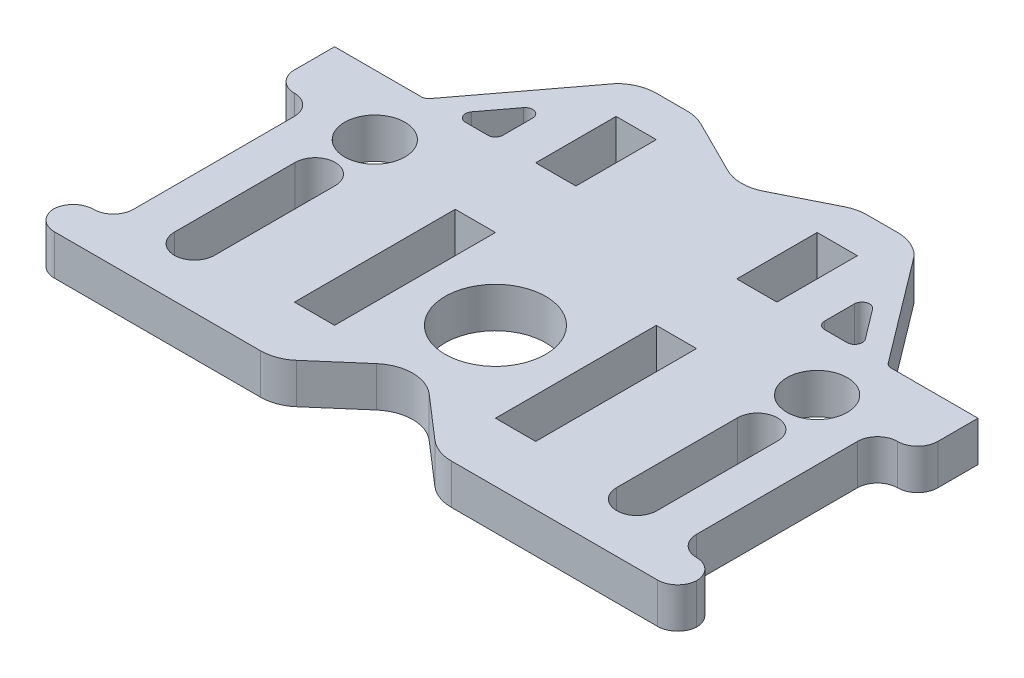
SolidWorks part; units mm, degrees
ref_plane "Front Plane" through (0, 0, 0) normal (0, 0, 1) x (1, 0, 0)
ref_plane "Top Plane" through (0, 0, 0) normal (0, 1, 0) x (1, 0, 0)
ref_plane "Right Plane" through (0, 0, 0) normal (1, 0, 0) x (0, 0, -1)
sketch "Sketch1" plane through (0, 0, 0) normal (0, 1, 0) x (1, 0, 0)
  line L0 (0, 12.7) -> (0, -12.7) construction
  line L1 (25.4, -12.7) -> (23.8125, -12.7)
  line L2 (25.4, -12.7) -> (25.4, -9.525)
  line L3 (25.4, 12.7) -> (23.8125, 12.7)
  line L4 (-25.4, -12.7) -> (-25.4, -9.525)
  line L5 (-25.4, -31.75) -> (-25.4, -12.7)
  line L6 (-6.35, 6.35) -> (-9.525, 6.35)
  line L7 (-6.35, 6.35) -> (-6.35, -6.35)
  line L8 (-6.35, -6.35) -> (-9.525, -6.35)
  line L9 (-9.525, 6.35) -> (-9.525, -6.35)
  line L10 (-3.175, -12.7) -> (-13.2935, -34.4304)
  line L11 (-19.05, -12.7) -> (-19.05, -22.225)
  line L12 (-15.0293, -23.1152) -> (-10.1796, -12.7)
  line L13 (-10.1796, -12.7) -> (-19.05, -12.7)
  line L14 (25.4, 0) -> (-25.4, 0) construction
  line L15 (-22.225, 6.35) -> (-22.225, -6.35)
  line L16 (-23.8125, 12.7) -> (-23.8125, -18.6877) construction
  line L17 (-25.4, 9.525) -> (-25.4, 12.7)
  line L18 (23.8125, 12.7) -> (23.8125, -18.6877) construction
  line L19 (25.4, 9.525) -> (25.4, 12.7)
  line L20 (22.225, 6.35) -> (22.225, -6.35)
  line L21 (10.1796, -12.7) -> (19.05, -12.7)
  line L22 (15.0293, -23.1152) -> (10.1796, -12.7)
  line L23 (19.05, -12.7) -> (19.05, -22.225)
  line L24 (3.175, -12.7) -> (13.2935, -34.4304)
  line L25 (9.525, 6.35) -> (9.525, -6.35)
  line L26 (6.35, -6.35) -> (9.525, -6.35)
  line L27 (6.35, 6.35) -> (6.35, -6.35)
  line L28 (6.35, 6.35) -> (9.525, 6.35)
  line L29 (25.4, -31.75) -> (25.4, -12.7)
  line L30 (25.4, -12.7) -> (25.4, -9.525)
  line L31 (25.4, 9.525) -> (25.4, 12.7)
  line L32 (3.175, -12.7) -> (-3.175, -12.7)
  line L33 (-6.35, 22.225) -> (-9.525, 22.225)
  line L34 (-6.35, 12.7) -> (-9.525, 12.7)
  line L35 (-6.35, 12.7) -> (-6.35, 19.05)
  line L36 (-6.35, 19.05) -> (-9.525, 19.05)
  line L37 (-9.525, 12.7) -> (-9.525, 19.05)
  line L38 (-23.8125, 12.7) -> (-18.2563, 12.7)
  line L39 (-6.35, 22.225) -> (0, 19.05)
  line L40 (16.2674, 12.7) -> (12.7, 12.7)
  line L41 (12.7, 17.4273) -> (16.2674, 12.7)
  line L42 (11.7701, 21.2951) -> (18.2563, 12.7)
  line L43 (6.35, 12.7) -> (9.525, 12.7)
  line L44 (-12.7, 12.7) -> (-12.7, 17.4273)
  line L45 (12.7, 12.7) -> (12.7, 17.4273)
  line L46 (-23.8125, 12.7) -> (-25.4, 12.7)
  line L47 (-6.35, 12.7) -> (-9.525, 12.7)
  line L48 (23.8125, 12.7) -> (18.2563, 12.7)
  line L49 (-11.7701, 21.2951) -> (-18.2563, 12.7)
  line L50 (-12.7, 17.4273) -> (-16.2674, 12.7)
  line L51 (-16.2674, 12.7) -> (-12.7, 12.7)
  line L52 (-10.5029, 20.3388) -> (-16.9891, 11.7437) construction
  line L53 (9.525, 12.7) -> (9.525, 19.05)
  line L54 (6.35, 12.7) -> (6.35, 19.05)
  line L55 (6.35, 12.7) -> (9.525, 12.7)
  line L56 (6.35, 22.225) -> (0, 19.05)
  line L57 (6.35, 19.05) -> (9.525, 19.05)
  line L58 (6.35, 22.225) -> (9.525, 22.225)
  circle A0 centre (-19.05, -31.75) radius 3.175
  arc A1 (-25.4, -31.75) -> (-13.2935, -34.4304) centre (-19.05, -31.75) ccw
  arc A2 (-15.0293, -23.1152) -> (-19.05, -22.225) centre (-19.05, -31.75) ccw
  circle A3 centre (-19.05, -31.75) radius 6.35 construction
  arc A4 (-23.8125, -7.9375) -> (-25.4, -9.525) centre (-23.8125, -9.525) ccw
  circle A5 centre (-19.05, -31.75) radius 9.525 construction
  arc A6 (-23.8125, -7.9375) -> (-22.225, -6.35) centre (-23.8125, -6.35) ccw
  arc A7 (-23.8125, 7.9375) -> (-22.225, 6.35) centre (-23.8125, 6.35) cw
  arc A8 (-23.8125, 7.9375) -> (-25.4, 9.525) centre (-23.8125, 9.525) cw
  arc A9 (23.8125, 7.9375) -> (25.4, 9.525) centre (23.8125, 9.525) ccw
  arc A10 (23.8125, 7.9375) -> (22.225, 6.35) centre (23.8125, 6.35) ccw
  arc A11 (23.8125, -7.9375) -> (22.225, -6.35) centre (23.8125, -6.35) cw
  arc A12 (23.8125, -7.9375) -> (25.4, -9.525) centre (23.8125, -9.525) cw
  arc A13 (15.0293, -23.1152) -> (19.05, -22.225) centre (19.05, -31.75) cw
  arc A14 (25.4, -31.75) -> (13.2935, -34.4304) centre (19.05, -31.75) cw
  circle A15 centre (19.05, -31.75) radius 3.175
  arc A16 (-11.7701, 21.2951) -> (-9.525, 22.225) centre (-9.525, 19.05) cw
  arc A17 (11.7701, 21.2951) -> (9.525, 22.225) centre (9.525, 19.05) ccw
  point P17 (-12.7, -31.75)
  point P21 (-9.525, -31.75)
  dimension "D7" = 6.35
  dimension "D1" = 50.8
  dimension "D2" = 25.4
  dimension "D3" = 3.175
  dimension "D4" = 12.7
  dimension "D5" = 6.35
  dimension "D6" = 6.35
  dimension "D8" = 44.45
  dimension "D9" = 19.05
  dimension "D11" = 3.175
  dimension "D13" = 6.35
  dimension "D14" = 6.35
  dimension "D15" = 3.175
  dimension "D16" = 1.5875
  dimension "D17" = 9.525
  dimension "D18" = 6.35
  dimension "D19" = 3.175
  dimension "D10" = 3.175
  dimension "D12" = 6.35
  dimension "D22" = 1.5875
extrude "Boss-Extrude1" add sketch "Sketch1" along normal blind 3.175 contours A14 L29 L2 A12 A11 L20 A10 A9 L19 L3 L17 A8 A7 L15 A6 A4 L4 L5 A1 L10 L32 L24 L12 A2 L11 L13 L27 L28 L25 L26 L9 L6 L7 L8 A0 A13 L22 L21 L23 A15 region at (0, 0, 5.8577)
fillet "Fillet1" radius 1.5875 6 edges at (19.05, 1.5875, 12.7) (10.1796, 1.5875, 12.7) (3.175, 1.5875, 12.7) (-3.175, 1.5875, 12.7) (-10.1796, 1.5875, 12.7) (-19.05, 1.5875, 12.7)
sketch "Sketch2" plane through (0, 3.175, 0) normal (0, 1, 0) x (1, 0, 0)
  line L0 (25.4, 12.7) -> (18.2563, 12.7) construction
  line L1 (-22.225, 6.35) -> (-22.225, -6.35) construction
  circle A0 centre (-17.4625, 7.9375) radius 2.3813
  circle A1 centre (17.4625, 7.9375) radius 2.3813
  dimension "D1" = 4.7625
  dimension "D2" = 4.7625
  dimension "D3" = 4.7625
extrude "Cut-Extrude1" cut sketch "Sketch2" against normal through all
fillet "Fillet2" radius 3.175 3 edges at (6.35, 1.5875, -22.225) (0, 1.5875, -19.05) (-6.35, 1.5875, -22.225)
fillet "Fillet4" radius 0.6 8 edges at (12.7, 1.5875, -12.7) (12.7, 1.5875, -17.4273) (-12.7, 1.5875, -17.4273) (-16.2674, 1.5875, -12.7) (-12.7, 1.5875, -12.7) (18.2563, 1.5875, -12.7) (16.2674, 1.5875, -12.7) (-18.2563, 1.5875, -12.7)
sketch "Sketch3" plane through (0, 3.175, 0) normal (0, 1, 0) x (1, 0, 0)
  line L1 (-31.6131, -11.0137) -> (27.6819, -11.0137)
  line L2 (-31.6131, -11.0137) -> (-31.6131, -41.4937)
  line L3 (-31.6131, -41.4937) -> (27.6819, -41.4937)
  line L4 (27.6819, -11.0137) -> (27.6819, -41.4937)
  dimension "D1" = 30.48
extrude "Cut-Extrude5" cut sketch "Sketch3" against normal through all
fillet "Fillet5" radius 1.5875 2 edges at (25.4, 1.5875, 11.0137) (-25.4, 1.5875, 11.0137)
sketch "Sketch4" plane through (0, 3.175, 0) normal (0, 1, 0) x (1, 0, 0)
  line L0 (-17.4625, 7.9375) -> (-17.4625, -11.0137) construction
  line L1 (23.8156, -11.0137) -> (-23.8156, -11.0137) construction
  line L2 (17.4625, 7.9375) -> (17.4625, -11.0137) construction
  line L3 (-17.4625, 3.2244) -> (-17.4625, -6.3006) construction
  line L4 (-15.875, 3.2244) -> (-15.875, -6.3006)
  line L5 (-19.05, 3.2244) -> (-19.05, -6.3006)
  line L6 (0, 19.4248) -> (0, -11.0137) construction
  line L7 (17.4625, 7.9375) -> (17.4625, -11.0137) construction
  line L8 (17.4625, 3.2244) -> (17.4625, -6.3006) construction
  line L9 (15.875, 3.2244) -> (15.875, -6.3006)
  line L10 (19.05, 3.2244) -> (19.05, -6.3006)
  arc A0 (-15.875, 3.2244) -> (-19.05, 3.2244) centre (-17.4625, 3.2244) ccw
  arc A1 (-19.05, -6.3006) -> (-15.875, -6.3006) centre (-17.4625, -6.3006) ccw
  arc A2 (-1.4199, 19.76) -> (1.4199, 19.76) centre (0, 22.5998) ccw construction
  arc A3 (15.875, 3.2244) -> (19.05, 3.2244) centre (17.4625, 3.2244) cw
  arc A4 (19.05, -6.3006) -> (15.875, -6.3006) centre (17.4625, -6.3006) cw
  point P10 (-17.4625, -1.5381)
  point P22 (17.4625, -1.5381)
  dimension "D1" = 1.5875
  dimension "D2" = 9.525
extrude "Cut-Extrude6" cut sketch "Sketch4" against normal through all
sketch "Sketch5" plane through (0, 3.175, 0) normal (0, 1, 0) x (1, 0, 0)
  line L0 (0, 0) -> (0, -11.0137) construction
  line L1 (23.8156, -11.0137) -> (-23.8156, -11.0137) construction
  line L2 (0, -5.5069) -> (-6.35, -11.0137)
  line L3 (0, -5.5069) -> (6.35, -11.0137)
  line L4 (-6.35, -11.0137) -> (6.35, -11.0137)
  circle A0 centre (0, 0) radius 3.9688
  dimension "D1" = 6.35
extrude "Cut-Extrude7" cut sketch "Sketch5" against normal through all
fillet "Fillet6" radius 3.175 3 edges at (6.35, 1.5875, 11.0137) (-6.35, 1.5875, 11.0137) (0, 1.5875, 5.5069)
